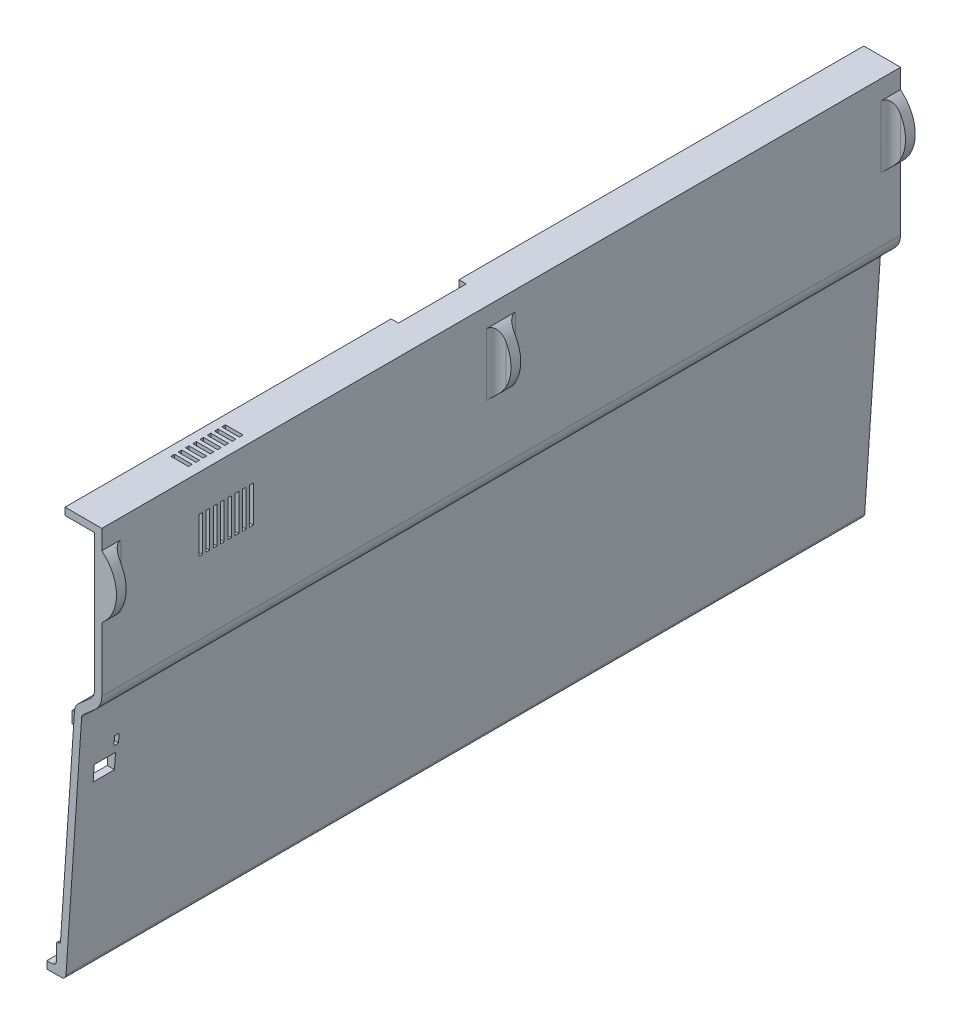
SolidWorks part; units mm, degrees
material "PET"
ref_plane "Front Plane" through (0, 0, 0) normal (0, 0, 1) x (1, 0, 0)
ref_plane "Top Plane" through (0, 0, 0) normal (0, 1, 0) x (1, 0, 0)
ref_plane "Right Plane" through (0, 0, 0) normal (1, 0, 0) x (0, 0, -1)
ref_plane "rightside" through (0, 0, 5) normal (0, 0, 1) x (1, 0, 0)
ref_plane "leftside" through (0, 0, -324.5) normal (0, 0, -1) x (-1, 0, 0)
sketch "masterprofile" plane through (0, 0, 0) normal (0, 0, 1) x (1, 0, 0)
  line L0 (-1347.2634, 866.31) -> (-1340.6373, 954.8362)
  line L1 (-1339.2576, 957.9262) -> (-1334.3763, 963.0092)
  line L2 (-1332.9827, 966.4725) -> (-1332.9827, 1017.7645)
  line L3 (-1352.2495, 861.6832) -> (-1353.5113, 861.6832)
  line L26 (-1358.5113, 866.6832) -> (-1358.5113, 1017.7645)
  line L29 (-1337.9827, 1025.7645) -> (-1353.5113, 1025.7645)
  line L30 (-1361.5113, 866.6832) -> (-1361.5113, 1017.7645)
  line L33 (-1352.2495, 858.6832) -> (-1353.5113, 858.6832)
  line L34 (-1344.2718, 866.0861) -> (-1337.6457, 954.6122)
  line L35 (-1337.9827, 1022.7645) -> (-1353.5113, 1022.7645)
  line L36 (-1337.0938, 955.8483) -> (-1332.2125, 960.9312)
  line L37 (-1329.9827, 966.4725) -> (-1329.9827, 1017.7645)
  arc A1 (-1352.2495, 861.6832) -> (-1347.2634, 866.31) centre (-1352.2495, 866.6832) ccw
  arc A5 (-1340.6373, 954.8362) -> (-1339.2576, 957.9262) centre (-1335.6513, 954.463) cw
  arc A6 (-1334.3763, 963.0092) -> (-1332.9827, 966.4725) centre (-1337.9827, 966.4725) ccw
  arc A8 (-1332.9827, 1017.7645) -> (-1337.9827, 1022.7645) centre (-1337.9827, 1017.7645) ccw
  arc A14 (-1353.5113, 1022.7645) -> (-1358.5113, 1017.7645) centre (-1353.5113, 1017.7645) ccw
  arc A15 (-1358.5113, 866.6832) -> (-1353.5113, 861.6832) centre (-1353.5113, 866.6832) ccw
  arc A16 (-1353.5113, 1025.7645) -> (-1361.5113, 1017.7645) centre (-1353.5113, 1017.7645) ccw
  arc A17 (-1361.5113, 866.6832) -> (-1353.5113, 858.6832) centre (-1353.5113, 866.6832) ccw
  arc A18 (-1352.2495, 858.6832) -> (-1344.2718, 866.0861) centre (-1352.2495, 866.6832) ccw
  arc A19 (-1337.6457, 954.6122) -> (-1337.0938, 955.8483) centre (-1335.6513, 954.463) cw
  arc A20 (-1332.2125, 960.9312) -> (-1329.9827, 966.4725) centre (-1337.9827, 966.4725) ccw
  arc A21 (-1329.9827, 1017.7645) -> (-1337.9827, 1025.7645) centre (-1337.9827, 1017.7645) ccw
  dimension "D1" = 5
  dimension "D2" = 3
  dimension "D4" = 5
sketch "bottomprofile" plane through (0, 0, 5) normal (0, 0, 1) x (1, 0, 0)
  line L0 (-1342.1552, 1022.7645) -> (-1332.9827, 1022.7645)
  line L2 (-1332.9827, 1022.7645) -> (-1332.9827, 966.4254)
  line L4 (-1334.6755, 962.6754) -> (-1339.5656, 958.3627)
  line L6 (-1341.247, 954.9502) -> (-1347.0441, 869.2406)
  line L12 (-1344.268, 866.0896) -> (-1338.3254, 953.9511)
  line L14 (-1337.5896, 955.4445) -> (-1332.6912, 959.7645)
  line L16 (-1329.9827, 965.7645) -> (-1329.9827, 1025.7645)
  line L18 (-1329.9827, 1025.7645) -> (-1345.1552, 1025.7645)
  line L26 (-1337.9827, 1025.7645) -> (-1353.5113, 1025.7645) construction
  line L31 (-1348.6163, 865.7243) -> (-1348.6163, 868.2743)
  line L32 (-1348.1163, 868.7743) -> (-1347.5429, 868.7743)
  line L38 (-1342.1552, 1022.7645) -> (-1345.1552, 1022.7645)
  line L39 (-1345.1552, 1022.7645) -> (-1345.1552, 1025.7645)
  line L41 (-1344.268, 866.0896) -> (-1344.7576, 858.8511)
  line L42 (-1346.753, 856.9861) -> (-1352.6662, 856.9861)
  line L43 (-1352.6662, 856.9861) -> (-1352.6662, 859.9861)
  line L44 (-1352.6662, 859.9861) -> (-1350.6163, 859.9861)
  line L45 (-1348.6163, 861.9861) -> (-1348.6163, 865.7243)
  arc A2 (-1332.9827, 966.4254) -> (-1334.6755, 962.6754) centre (-1337.9827, 966.4254) cw
  arc A3 (-1329.9827, 965.7645) -> (-1332.6912, 959.7645) centre (-1337.9827, 965.7645) cw
  arc A4 (-1337.5896, 955.4445) -> (-1338.3254, 953.9511) centre (-1336.1424, 953.8034) ccw
  arc A5 (-1339.5656, 958.3627) -> (-1341.247, 954.9502) centre (-1336.2584, 954.6127) ccw
  arc A17 (-1347.0441, 869.2406) -> (-1347.5429, 868.7743) centre (-1347.5429, 869.2743) cw
  arc A18 (-1348.6163, 868.2743) -> (-1348.1163, 868.7743) centre (-1348.1163, 868.2743) cw
  arc A20 (-1344.7576, 858.8511) -> (-1346.753, 856.9861) centre (-1346.753, 858.9861) cw
  arc A21 (-1348.6163, 861.9861) -> (-1350.6163, 859.9861) centre (-1350.6163, 861.9861) cw
  point P11 (-1344.8837, 856.9861)
  dimension "D9" = 6
  dimension "D16" = 0.5
  dimension "D6" = 2
  dimension "D8" = 2
  dimension "D3" = 3
  dimension "D4" = 4.3483
  dimension "D5" = 3
  dimension "D7" = 60
extrude "bottomplate" add sketch "bottomprofile" against normal up to surface (329.5 mm away) up to plane "leftside"
sketch "Sketch32" plane through (-1332.9827, 0, 0) normal (-1, 0, 0) x (0, 0, 1)
  line L1 (-89.6797, 1015.7584) -> (-2.5397, 1015.7584)
  line L3 (-87.9297, 1012.2584) -> (-4.2897, 1012.2584)
  line L9 (-87.9297, 970.7584) -> (-4.2897, 970.7584)
  line L11 (-89.6797, 967.2584) -> (-2.5397, 967.2584)
  line L14 (-91.4297, 1014.0084) -> (-91.4297, 969.0084)
  line L16 (-87.9297, 1012.2584) -> (-87.9297, 970.7584)
  line L18 (-4.2897, 1012.2584) -> (-4.2897, 970.7584)
  line L20 (-0.7897, 1014.0084) -> (-0.7897, 969.0084)
  arc A0 (-91.4297, 1014.0084) -> (-89.6797, 1015.7584) centre (-89.6797, 1014.0084) cw
  arc A1 (-2.5397, 1015.7584) -> (-0.7897, 1014.0084) centre (-2.5397, 1014.0084) cw
  arc A2 (-0.7897, 969.0084) -> (-2.5397, 967.2584) centre (-2.5397, 969.0084) cw
  arc A3 (-91.4297, 969.0084) -> (-89.6797, 967.2584) centre (-89.6797, 969.0084) ccw
  dimension "D1" = 3.5
  dimension "D2" = 3.5
  dimension "D3" = 3.5
  dimension "D4" = 3.5
ref_plane "fpgalimit" through (0, 0, -110) normal (0, 0, 1) x (1, 0, 0)
sketch "fpgabase" plane through (-1332.9827, 0, 0) normal (-1, 0, 0) x (0, 0, 1)
  circle A4 centre (-89.6006, 968.9435) radius 3.7831
  circle A5 centre (-89.6006, 1013.9435) radius 3.75
  circle A6 centre (-2.4606, 1013.9435) radius 3.75
  circle A7 centre (-2.4606, 968.9435) radius 3.75
  circle A8 centre (-2.4606, 1013.9435) radius 1
  circle A9 centre (-2.4606, 968.9435) radius 1
  circle A10 centre (-89.6006, 1013.9435) radius 1
  circle A11 centre (-89.6006, 968.9435) radius 1
extrude "fpgasupportbottom" add sketch "fpgabase" along normal blind 3.3
sketch "Sketch19" plane through (0, 1025.7645, 0) normal (0, 1, 0) x (1, 0, 0)
  line L1 (-1334.2002, 36.5) -> (-1341.5051, 36.5)
  line L2 (-1334.2002, 36.5) -> (-1334.2002, 35)
  line L3 (-1334.2002, 35) -> (-1341.5051, 35)
  line L4 (-1341.5051, 36.5) -> (-1341.5051, 35)
  line L5 (-36.8795, -5) -> (36.8795, -5) construction
  line L6 (-1334.2002, 39.5) -> (-1341.5051, 39.5)
  line L7 (-1334.2002, 39.5) -> (-1334.2002, 38)
  line L8 (-1334.2002, 38) -> (-1341.5051, 38)
  line L9 (-1341.5051, 39.5) -> (-1341.5051, 38)
  line L10 (-1334.2002, 42.5) -> (-1341.5051, 42.5)
  line L11 (-1334.2002, 42.5) -> (-1334.2002, 41)
  line L12 (-1334.2002, 41) -> (-1341.5051, 41)
  line L13 (-1341.5051, 42.5) -> (-1341.5051, 41)
  line L14 (-1334.2002, 45.5) -> (-1341.5051, 45.5)
  line L15 (-1334.2002, 45.5) -> (-1334.2002, 44)
  line L16 (-1334.2002, 44) -> (-1341.5051, 44)
  line L17 (-1341.5051, 45.5) -> (-1341.5051, 44)
  line L18 (-1334.2002, 48.5) -> (-1341.5051, 48.5)
  line L19 (-1334.2002, 48.5) -> (-1334.2002, 47)
  line L20 (-1334.2002, 47) -> (-1341.5051, 47)
  line L21 (-1341.5051, 48.5) -> (-1341.5051, 47)
  line L22 (-1334.2002, 51.5) -> (-1341.5051, 51.5)
  line L23 (-1334.2002, 51.5) -> (-1334.2002, 50)
  line L24 (-1334.2002, 50) -> (-1341.5051, 50)
  line L25 (-1341.5051, 51.5) -> (-1341.5051, 50)
  line L26 (-1334.2002, 54.5) -> (-1341.5051, 54.5)
  line L27 (-1334.2002, 54.5) -> (-1334.2002, 53)
  line L28 (-1334.2002, 53) -> (-1341.5051, 53)
  line L29 (-1341.5051, 54.5) -> (-1341.5051, 53)
  line L30 (-1334.2002, 57.5) -> (-1341.5051, 57.5)
  line L31 (-1334.2002, 57.5) -> (-1334.2002, 56)
  line L32 (-1334.2002, 56) -> (-1341.5051, 56)
  line L33 (-1341.5051, 57.5) -> (-1341.5051, 56)
  dimension "D1" = 40
  dimension "D2" = 1.5
  dimension "D3" = 8
extrude "airventback" cut sketch "Sketch19" against normal blind 10
sketch "Sketch20" plane through (-1329.9827, 0, 0) normal (1, 0, 0) x (0, 0, -1)
  line L0 (38, 1010.7163) -> (39.5, 1010.7163)
  line L1 (35, 1010.7163) -> (36.5, 1010.7163)
  line L2 (35, 1010.7163) -> (35, 995.7163)
  line L3 (35, 995.7163) -> (36.5, 995.7163)
  line L4 (36.5, 1010.7163) -> (36.5, 995.7163)
  line L5 (38, 1010.7163) -> (38, 995.7163)
  line L6 (38, 995.7163) -> (39.5, 995.7163)
  line L7 (39.5, 1010.7163) -> (39.5, 995.7163)
  line L8 (41, 1010.7163) -> (42.5, 1010.7163)
  line L9 (41, 1010.7163) -> (41, 995.7163)
  line L10 (41, 995.7163) -> (42.5, 995.7163)
  line L11 (42.5, 1010.7163) -> (42.5, 995.7163)
  line L12 (44, 1010.7163) -> (45.5, 1010.7163)
  line L13 (44, 1010.7163) -> (44, 995.7163)
  line L14 (44, 995.7163) -> (45.5, 995.7163)
  line L15 (45.5, 1010.7163) -> (45.5, 995.7163)
  line L16 (47, 1010.7163) -> (48.5, 1010.7163)
  line L17 (47, 1010.7163) -> (47, 995.7163)
  line L18 (47, 995.7163) -> (48.5, 995.7163)
  line L19 (48.5, 1010.7163) -> (48.5, 995.7163)
  line L20 (50, 1010.7163) -> (51.5, 1010.7163)
  line L21 (50, 1010.7163) -> (50, 995.7163)
  line L22 (50, 995.7163) -> (51.5, 995.7163)
  line L23 (51.5, 1010.7163) -> (51.5, 995.7163)
  line L24 (53, 1010.7163) -> (54.5, 1010.7163)
  line L25 (53, 1010.7163) -> (53, 995.7163)
  line L26 (53, 995.7163) -> (54.5, 995.7163)
  line L27 (54.5, 1010.7163) -> (54.5, 995.7163)
  line L28 (56, 1010.7163) -> (57.5, 1010.7163)
  line L29 (56, 1010.7163) -> (56, 995.7163)
  line L30 (56, 995.7163) -> (57.5, 995.7163)
  line L31 (57.5, 1010.7163) -> (57.5, 995.7163)
  dimension "D1" = 1.5
  dimension "D2" = 15
extrude "airventbottom" cut sketch "Sketch20" against normal blind 4
ref_plane "middleplane" through (0, 0, -159.75) normal (0, 0, 1) x (1, 0, 0)
sketch "Sketch22" plane through (0, 0, 5) normal (0, 0, 1) x (1, 0, 0)
  line L0 (-1329.9827, 1017.7645) -> (-1329.9827, 992.1185)
  arc A0 (-1329.9827, 1017.7645) -> (-1329.9827, 992.1185) centre (-1340.5014, 1004.9415) cw
extrude "rightleg" add sketch "Sketch22" against normal blind 4
mirror "legmirror" about plane through (0, 0, -159.75) normal (0, 0, 1) of "rightleg"
sketch "Sketch25" plane through (-1332.9827, 0, 0) normal (-1, 0, 0) x (0, 0, 1)
  line L0 (-120.3318, 1013.7645) -> (-316.4128, 1013.7645)
  line L1 (-316.4128, 1013.7645) -> (-316.4128, 1012.2645)
  line L2 (-316.4128, 1012.2645) -> (-120.3318, 1012.2645)
  line L3 (-120.3318, 1012.2645) -> (-120.3318, 1013.7645)
  line L4 (-324.5, 1025.7645) -> (5, 1025.7645) construction
  line L5 (-120.3318, 1005.1398) -> (-316.4128, 1005.1398)
  line L6 (-316.4128, 1005.1398) -> (-316.4128, 1003.6398)
  line L7 (-316.4128, 1003.6398) -> (-120.3318, 1003.6398)
  line L8 (-120.3318, 1003.6398) -> (-120.3318, 1005.1398)
  line L9 (-120.3318, 996.5152) -> (-316.4128, 996.5152)
  line L10 (-316.4128, 996.5152) -> (-316.4128, 995.0152)
  line L11 (-316.4128, 995.0152) -> (-120.3318, 995.0152)
  line L12 (-120.3318, 995.0152) -> (-120.3318, 996.5152)
  line L13 (-120.3318, 987.8906) -> (-316.4128, 987.8906)
  line L14 (-316.4128, 987.8906) -> (-316.4128, 986.3906)
  line L15 (-316.4128, 986.3906) -> (-120.3318, 986.3906)
  line L16 (-120.3318, 986.3906) -> (-120.3318, 987.8906)
  dimension "D1" = 1.5
  dimension "D2" = 12
extrude "uppperfins" add sketch "Sketch25" along normal blind 2
fillet "upperfinfillet" radius 2 8 edges at (-1332.9827, 1013.7645, -218.3723) (-1332.9827, 1005.1398, -218.3723) (-1332.9827, 996.5152, -218.3723) (-1332.9827, 987.8906, -218.3723) (-1332.9827, 986.3906, -218.3723) (-1332.9827, 995.0152, -218.3723) (-1332.9827, 1003.6398, -218.3723) (-1332.9827, 1012.2645, -218.3723)
extrude "fpgasupportframe" add sketch "Sketch32" along normal blind 1.5
sketch "Sketch39" plane through (-1334.4827, 0, 0) normal (-1, 0, 0) x (0, 0, 1)
  circle A0 centre (-91.6483, 1013.9604) radius 1
  circle A1 centre (-4.5083, 1013.9604) radius 1
  circle A2 centre (-4.5083, 968.9604) radius 1
  circle A3 centre (-91.6483, 968.9604) radius 1
extrude "fpgascrewholes" cut sketch "Sketch39" against normal blind 1 and the other way blind 1
sketch "Sketch41" plane through (-1345.1552, 0, 0) normal (-1, 0, 0) x (0, 0, 1)
  line L1 (-157.5, 1029.389) -> (-129.5, 1029.389)
  line L2 (-157.5, 1029.389) -> (-157.5, 1019.389)
  line L3 (-157.5, 1019.389) -> (-129.5, 1019.389)
  line L4 (-129.5, 1029.389) -> (-129.5, 1019.389)
extrude "sdcardhole" cut sketch "Sketch41" against normal blind 3
sketch "Sketch42" plane through (-1342.1552, 0, 0) normal (-1, 0, 0) x (0, 0, 1)
  line L1 (-157.4961, 1025.7645) -> (-145.4961, 1025.7645)
  line L2 (-157.4961, 1025.7645) -> (-157.4961, 1005.7645)
  line L3 (-157.4961, 1005.7645) -> (-145.4961, 1005.7645)
  line L4 (-145.4961, 1025.7645) -> (-145.4961, 1005.7645)
  line L5 (-129.4961, 1025.7645) -> (-141.4961, 1025.7645)
  line L6 (-129.4961, 1025.7645) -> (-129.4961, 1005.7645)
  line L7 (-129.4961, 1005.7645) -> (-141.4961, 1005.7645)
  line L8 (-141.4961, 1025.7645) -> (-141.4961, 1005.7645)
  line L10 (-157.5, 1025.7645) -> (-129.5, 1025.7645) construction
  line L11 (-110, -45.1713) -> (-110, 45.1713) construction
  dimension "D5" = 12
  dimension "D1" = 20
  dimension "D2" = 20
  dimension "D3" = 19.4961
  dimension "D4" = 12
extrude "sdcardbase" add sketch "Sketch42" against normal up to next
ref_plane "Plane5" through (0, 0, -159.75) normal (0, 0, 1) x (1, 0, 0)
sketch "Sketch43" plane through (0, 0, -159.75) normal (0, 0, 1) x (1, 0, 0)
  line L0 (-1329.9827, 1017.7645) -> (-1331.369, 1017.7645)
  line L1 (-1331.369, 1017.7645) -> (-1331.369, 992.1185)
  line L2 (-1331.369, 992.1185) -> (-1329.9827, 992.1185)
  arc A0 (-1329.9827, 1017.7645) -> (-1329.9827, 992.1185) centre (-1340.5014, 1004.9415) cw
extrude "midleg" add sketch "Sketch43" along normal blind 2 and the other way blind 2
fillet "legfillet" radius 4 4 edges at (-1329.9827, 1004.9415, 1) (-1329.9827, 1004.9415, -320.5) (-1329.9827, 1004.9415, -161.75) (-1329.9827, 1004.9415, -157.75)
sketch "Sketch54" plane through (-1348.6163, 0, 0) normal (-1, 0, 0) x (0, 0, 1)
  circle A0 centre (-315.5, 870.0243) radius 4
  circle A1 centre (-3.9, 870.0243) radius 4
extrude "pcbsupportbottom" add sketch "Sketch54" against normal up to next
sketch "Sketch55" plane through (-1348.6163, 0, 0) normal (1, 0, 0) x (0, 0, -1)
  line L2 (311.5599, 965.8998) -> (319.2039, 965.8998)
  line L3 (311.5599, 965.8998) -> (311.5599, 972.1019)
  line L4 (311.5599, 972.1019) -> (319.2039, 972.1019)
  line L5 (319.2039, 965.8998) -> (319.2039, 972.1019)
  line L10 (1.3734, 948.2542) -> (12.6046, 948.2542)
  line L11 (1.3734, 948.2542) -> (1.3734, 943.4939)
  line L12 (1.3734, 943.4939) -> (12.6046, 943.4939)
  line L13 (12.6046, 948.2542) -> (12.6046, 943.4939)
extrude "Boss-Extrude1" add sketch "Sketch55" along normal up to next
sketch "Sketch56" plane through (-1348.6163, 0, 0) normal (-1, 0, 0) x (0, 0, 1)
  circle A0 centre (-315.5, 967.7743) radius 0.9
extrude "pcbtopscrew" cut sketch "Sketch56" against normal blind 7
sketch "Sketch57" plane through (-1346.0313, 0, 0) normal (1, 0, 0) x (0, 0, -1)
  line L1 (9.5577, 936.062) -> (9.5577, 935.7653) construction
  line L2 (9.5577, 939.7366) -> (11.4423, 939.7366)
  line L3 (9.5577, 939.7366) -> (9.5577, 936.062)
  line L4 (9.5577, 936.062) -> (11.4423, 936.062)
  line L5 (11.4423, 939.7366) -> (11.4423, 936.062)
  line L6 (11.4423, 936.062) -> (9.5577, 936.062) construction
  line L7 (11.4423, 939.7366) -> (11.739, 939.7366) construction
  line L8 (11.4423, 939.7366) -> (11.4423, 936.062) construction
  point P0 (11.4423, 939.7366)
extrude "Cut-Extrude2" cut sketch "Sketch57" along normal blind 10
sketch "Sketch58" plane through (-1345.9913, 0, 0) normal (1, 0, 0) x (0, 0, -1)
  line L2 (10.4072, 933.1939) -> (1.6121, 933.1939)
  line L3 (10.4072, 933.1939) -> (10.4072, 926.7759)
  line L4 (10.4072, 926.7759) -> (1.6121, 926.7759)
  line L5 (1.6121, 933.1939) -> (1.6121, 926.7759)
extrude "Cut-Extrude3" cut sketch "Sketch58" along normal blind 10
